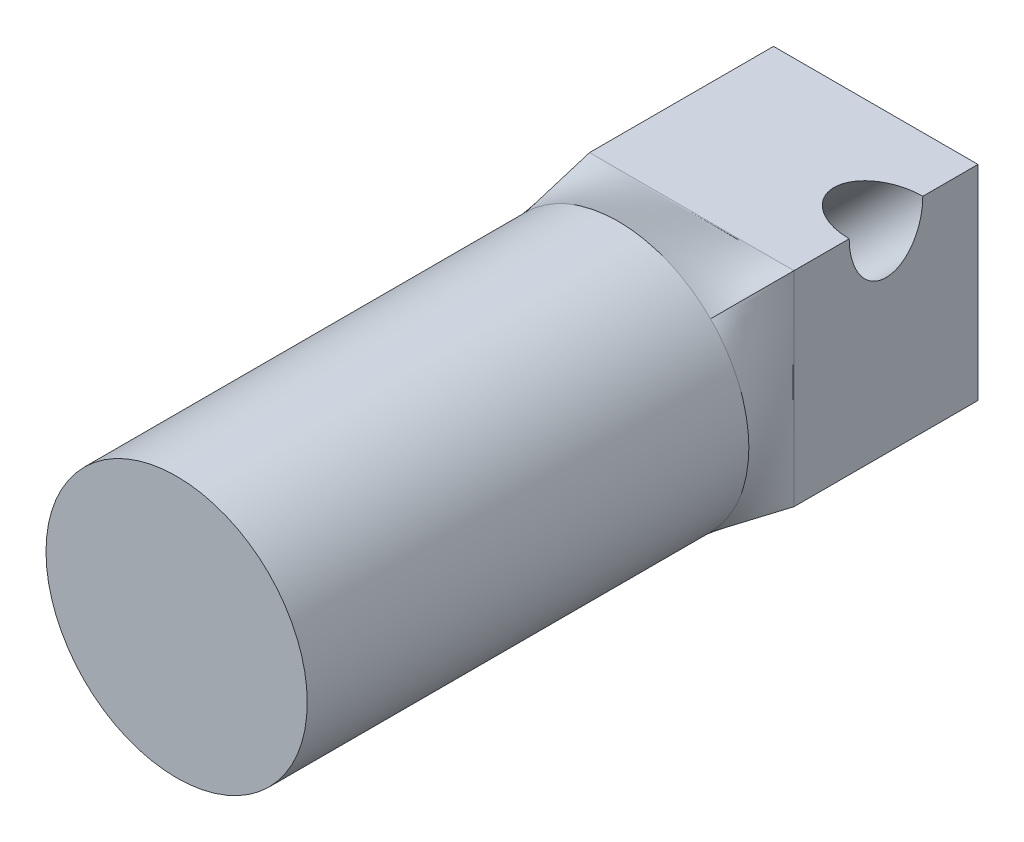
SolidWorks part; units mm, degrees
ref_plane "Front Plane" through (0, 0, 0) normal (0, 0, 1) x (1, 0, 0)
ref_plane "Top Plane" through (0, 0, 0) normal (0, 1, 0) x (1, 0, 0)
ref_plane "Right Plane" through (0, 0, 0) normal (1, 0, 0) x (0, 0, -1)
sketch "Sketch1" plane through (0, 0, 0) normal (0, 0, 1) x (1, 0, 0)
  line L0 (0, 0) -> (-2.4749, 2.4749) construction
  line L1 (2.8284, -2.8284) -> (-2.8284, -2.8284) construction
  line L2 (2.8284, -2.8284) -> (2.8284, 2.8284) construction
  line L3 (2.8284, 2.8284) -> (-2.8284, 2.8284) construction
  line L4 (-2.8284, -2.8284) -> (-2.8284, 2.8284) construction
  line L5 (2.8284, -2.8284) -> (-2.8284, 2.8284) construction
  line L6 (2.8284, 2.8284) -> (-2.8284, -2.8284) construction
  line L7 (2.7784, 2.7784) -> (-2.7784, 2.7784)
  line L8 (-2.7784, -2.7784) -> (-2.7784, 2.7784)
  line L9 (2.7784, -2.7784) -> (-2.7784, -2.7784)
  line L10 (2.7784, -2.7784) -> (2.7784, 2.7784)
  point P0 (0, 0)
  dimension "D1" = 3.5
  dimension "D2" = 0.5
  dimension "D3" = 0.05
ref_plane "Plane1" through (0, 0, 2) normal (0, 0, 1) x (1, 0, 0)
sketch "Sketch2" plane through (0, 0, 2) normal (0, 0, 1) x (1, 0, 0)
  circle A0 centre (0, 0) radius 3.55
  dimension "D1" = 7.1
loft "Loft1" add profiles "Sketch1", "Sketch2" connector at (-2.7784, 2.7784, 0) connector at (-1.7258, 3.1023, 2)
sketch "Sketch3" plane through (0, 0, 0) normal (0, 0, -1) x (-1, 0, 0)
  line L4 (-2.7784, 2.7784) -> (-2.7784, -2.7784)
  line L5 (-2.7784, -2.7784) -> (2.7784, -2.7784)
  line L6 (2.7784, -2.7784) -> (2.7784, 2.7784)
  line L7 (2.7784, 2.7784) -> (-2.7784, 2.7784)
  line L8 (-2.7784, 2.7784) -> (-2.7784, -2.7784)
  line L9 (-2.7784, -2.7784) -> (2.7784, -2.7784)
  line L10 (2.7784, -2.7784) -> (2.7784, 2.7784)
  line L11 (2.7784, 2.7784) -> (-2.7784, 2.7784)
  dimension "D1" = 0
extrude "Boss-Extrude1" add sketch "Sketch3" along normal blind 5
sketch "Sketch4" plane through (0, 0, 2) normal (0, 0, 1) x (1, 0, 0)
  arc A4 (2.5102, 2.5102) -> (-2.5102, 2.5102) centre (0, 0) ccw
  arc A5 (-2.5102, 2.5102) -> (-2.5102, -2.5102) centre (0, 0) ccw
  arc A6 (-2.5102, -2.5102) -> (2.5102, -2.5102) centre (0, 0) ccw
  arc A7 (2.5102, -2.5102) -> (2.5102, 2.5102) centre (0, 0) ccw
  arc A8 (2.5102, 2.5102) -> (-2.5102, 2.5102) centre (0, 0) ccw
  arc A9 (-2.5102, 2.5102) -> (-2.5102, -2.5102) centre (0, 0) ccw
  arc A10 (-2.5102, -2.5102) -> (2.5102, -2.5102) centre (0, 0) ccw
  arc A11 (2.5102, -2.5102) -> (2.5102, 2.5102) centre (0, 0) ccw
  dimension "D1" = 0
extrude "Boss-Extrude2" add sketch "Sketch4" along normal blind 12
ref_axis "Axis1" through (0, 0, 14) along (0, 0, -1)
ref_plane "Plane2" through (0, 0, 0) normal (0.7071, 0.7071, 0) x (0, 0, -1)
sketch "Sketch5" plane through (0, 0, 0) normal (0.7071, 0.7071, 0) x (0, 0, -1)
  line L0 (5, 0) -> (0, 0) construction
  circle A0 centre (2.5, 0) radius 1
  dimension "D1" = 2
extrude "Cut-Extrude1" cut sketch "Sketch5" against normal mid plane 10
